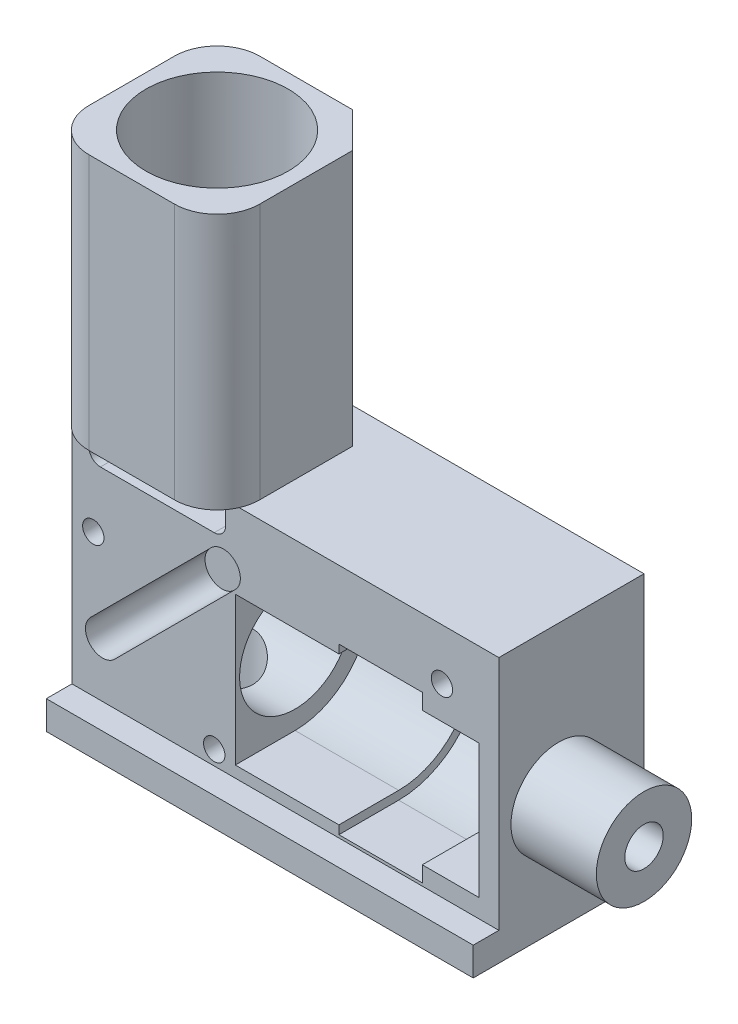
SolidWorks part; units mm, degrees
ref_plane "Front Plane" through (0, 0, 0) normal (0, 0, 1) x (1, 0, 0)
ref_plane "Top Plane" through (0, 0, 0) normal (0, 1, 0) x (1, 0, 0)
ref_plane "Right Plane" through (0, 0, 0) normal (1, 0, 0) x (0, 0, -1)
sketch "Sketch1" plane through (0, 0, 0) normal (0, 1, 0) x (1, 0, 0)
  line L1 (7.5, 3) -> (-7.5, 3)
  line L2 (7.5, 3) -> (7.5, -3)
  line L3 (7.5, -3) -> (-7.5, -3)
  line L4 (-7.5, 3) -> (-7.5, -3)
  line L5 (7.5, 3) -> (-7.5, -3) construction
  line L6 (7.5, -3) -> (-7.5, 3) construction
  point P0 (0, 0)
  dimension "D1" = 6
  dimension "D2" = 15
extrude "Main Body Ext" add sketch "Sketch1" along normal blind 9.3
sketch "Sketch8" plane through (0, 9.3, 0) normal (0, 1, 0) x (1, 0, 0)
  line L0 (-2.75, 3) -> (-1.5, 1.75)
  line L1 (-2.75, 3) -> (-7.5, 3)
  line L2 (-1.5, 1.75) -> (-1.5, -3)
  line L3 (-1.5, -3) -> (-7.5, -3)
  line L4 (-7.5, 3) -> (-7.5, -3)
  line L5 (-2.125, 2.375) -> (-7.5, -3) construction
  line L6 (-1.5, -3) -> (-7.5, 3) construction
  line L7 (-7.5, 3) -> (-7.5, -3) construction
  line L8 (0, 0) -> (-4.5, 0) construction
  point P0 (-4.5, 0)
  dimension "D1" = 6
  dimension "D2" = 6
  dimension "D3" = 1.25
  dimension "D4" = 3
extrude "Emission Path Ext" add sketch "Sketch8" along normal blind 9
sketch "Sketch3" plane through (0, 0, 0) normal (0, -1, 0) x (1, 0, 0)
  line L0 (-7.5, -3) -> (-7.5, 3) construction
  line L1 (0, 0) -> (-4.5, 0) construction
  circle A0 centre (-4.5, 0) radius 1.25
  dimension "D1" = 3
  dimension "D2" = 2.5
extrude "Emission and Grin Cut" cut sketch "Sketch3" against normal through all
sketch "Sketch4" plane through (7.5, 0, 0) normal (1, 0, 0) x (0, 0, -1)
  line L1 (-3, 0) -> (3, 0) construction
  circle A0 centre (0, 4) radius 0.675
  dimension "D1" = 1.35
  dimension "D2" = 4
extrude "Fiber Ferrule Cut" cut sketch "Sketch4" against normal offset from surface (13 mm away) 2 up to face at (-7.5, 9.15, 0)
sketch "Sketch41" plane through (7.5, 0, 0) normal (1, 0, 0) x (0, 0, -1)
  circle A0 centre (0, 4) radius 1.675
  circle A1 centre (0, 4) radius 0.675 construction
  circle A2 centre (0, 4) radius 0.675
  dimension "D1" = 1
extrude "Fiber Ferrule Port Ext" add sketch "Sketch41" along normal blind 3
sketch "Sketch5" plane through (0, 0, 3) normal (0, 0, 1) x (1, 0, 0)
  line L0 (-7.5, 0) -> (7.5, 0) construction
  line L1 (7.5, 9.3) -> (-7.5, 9.3)
  line L2 (7.5, 9.3) -> (7.5, 1)
  line L3 (7.5, 1) -> (-7.5, 1)
  line L4 (-7.5, 9.3) -> (-7.5, 1)
  line L5 (7.5, 9.3) -> (-7.5, 1) construction
  line L6 (7.5, 1) -> (-7.5, 9.3) construction
  line L7 (-1.5, 9.3) -> (7.5, 9.3) construction
  line L9 (7.5, 9.3) -> (7.5, 0) construction
  line L10 (-7.5, 18.3) -> (-7.5, 0) construction
  point P0 (0, 5.15)
  dimension "D1" = 1
extrude "FilterSet Cut1" cut sketch "Sketch5" against normal blind 0.9
sketch "Sketch6" plane through (0, 0, 2.1) normal (0, 0, 1) x (1, 0, 0)
  line L0 (3.4, 7.5) -> (3.4, 1.5)
  line L1 (3.4, 1.5) -> (-0.9, 1.5)
  line L3 (-7.5, 1) -> (7.5, 1) construction
  line L4 (-7.5, 9.3) -> (-7.5, 1) construction
  line L5 (-6.9, 8.9) -> (-6.9, 8.5)
  line L7 (-1.5, 9.3) -> (-7.5, 9.3) construction
  line L8 (-2.1, 8.9) -> (-2.1, 8.5)
  line L9 (-6, 2.5) -> (-6, 1) construction
  line L10 (-2.5, 9.3) -> (-6.5, 9.3)
  line L11 (-4.5, 4) -> (-4.5, 1) construction
  line L12 (-4.5, 4) -> (0.4851, 4) construction
  line L13 (-2.5, 8.1) -> (-6.5, 8.1)
  line L14 (-0.9, 1.5) -> (-0.9, 7.5)
  line L15 (-2.5, 9.3) -> (-6.5, 8.1) construction
  line L16 (-2.5, 8.1) -> (-6.5, 9.3) construction
  line L18 (-2.6059, 7.5912) -> (-6.8485, 3.3485)
  line L20 (-1.7574, 6.7426) -> (-6, 2.5)
  line L21 (-2.6059, 7.5912) -> (-6, 2.5) construction
  line L22 (-6.8485, 3.3485) -> (-1.7574, 6.7426) construction
  line L24 (-0.9, 7.5) -> (3.4, 7.5)
  line L33 (-2.5, 9.3) -> (1.102, 9.3) construction
  line L35 (1.102, 8.1) -> (-2.5, 8.1) construction
  line L36 (-6.5, 8.1) -> (-4.098, 8.1) construction
  line L38 (-4.098, 9.3) -> (-6.5, 9.3) construction
  arc A0 (-2.5, 9.3) -> (-2.1, 8.9) centre (-2.5, 8.9) cw
  arc A2 (-6.5, 9.3) -> (-6.9, 8.9) centre (-6.5, 8.9) ccw
  arc A3 (-2.6059, 7.5912) -> (-1.7574, 6.7426) centre (-2.1816, 7.1669) cw
  arc A5 (-6.8485, 3.3485) -> (-6, 2.5) centre (-6.4243, 2.9243) ccw
  arc A7 (-6.5, 8.1) -> (-6.9, 8.5) centre (-6.5, 8.5) cw
  arc A8 (-2.5, 8.1) -> (-2.1, 8.5) centre (-2.5, 8.5) ccw
  point P5 (-4.5, 8.7)
  point P10 (-4.3029, 5.0456)
  point P24 (-0.6861, 4)
  point P48 (-0.9, 4.5)
  line M12 (-1.5, 9.3) -> (-7.5, 9.3)
  dimension "D10" = 1.5
  dimension "D5" = 6.6
  dimension "D8" = 0.5
  dimension "D11" = 0.4
  dimension "D12" = 0.4
  dimension "D2" = 45
  dimension "D3" = 6
  dimension "D4" = 1.2
  dimension "D6" = 3
  dimension "D7" = 4
  dimension "D9" = 3
  dimension "D13" = 1.2
  dimension "D14" = 3
  dimension "D15" = 6
  dimension "D17" = 4.3
extrude "FilterSet Cut2" cut sketch "Sketch6" against normal offset from surface (4.2 mm away) 0.9 contours L18 A5 L20 A3 | L13 A8 L8 A0 A2 L5 A7 M12 up to face at (-0.0625, 9.95, -3)
sketch "Sketch39" plane through (0, 0, 0) normal (0, 0, 1) x (1, 0, 0)
  line L0 (-4.5, 4) -> (0.4851, 4) construction
  line L1 (-4.5, 4) -> (-0.9, 4) construction
  line L2 (0.6, 6.6) -> (1.88, 6.6)
  line L3 (1.88, 6.6) -> (1.88, 6.9)
  line L5 (3.4, 7.5) -> (3.4, 1.5) construction
  line L6 (3.4, 6.9) -> (4.81, 6.9)
  line L8 (4.81, 4) -> (3.4, 4)
  line L10 (3.4, 6.9) -> (1.88, 6.9)
  line L12 (3.4, 4) -> (-0.4058, 4)
  line L16 (-0.9, 6.6) -> (-1.76, 6.6)
  line L17 (-1.76, 6.6) -> (-1.76, 4)
  line L18 (-1.76, 4) -> (-0.9, 4)
  line L19 (-0.9, 6.6) -> (0.6, 6.6)
  line L22 (-0.5058, 4) -> (0.4851, 4) construction
  line L23 (-0.9, 4) -> (-0.4058, 4)
  line L24 (4.81, 4) -> (6.967, 4) construction
  line L26 (4.81, 4) -> (4.81, 6.9) construction
  line L27 (4.81, 4) -> (6.81, 4)
  line L30 (6.81, 4) -> (6.81, 6.35)
  line L31 (6.81, 6.35) -> (4.81, 6.35)
  line L32 (4.81, 6.35) -> (4.81, 6.9)
  dimension "D1" = 2.93
  dimension "D3" = 2.6
  dimension "D4" = 6.57
  dimension "D5" = 0.55
  dimension "D6" = 2
  dimension "D7" = 2.74
  dimension "D8" = 2.9
revolve "Excitation Lens Cut" cut sketch "Sketch39" angle 360 about L8
sketch "Sketch10" plane through (0, 18.3, 0) normal (0, 1, 0) x (1, 0, 0)
  line L0 (-4.5, 0) -> (-4.5, -3) construction
  line L1 (-7.5, -3) -> (-1.5, -3) construction
  line L3 (-4.5, 0) -> (-7.5, 0) construction
  line L4 (-7.5, 3) -> (-7.5, -3) construction
  circle A0 centre (-4.5, 0) radius 2.5
  dimension "D1" = 5
extrude "Emission Lens Cut" cut sketch "Sketch10" against normal offset from surface (8.5 mm away) 0.5 up to face at (-4.125, 9.3, 1.3313)
sketch "Sketch40" plane through (-1.76, 0, 0) normal (1, 0, 0) x (0, 0, -1)
  circle A0 centre (0, 4) radius 1.95
  dimension "D1" = 3.9
extrude "Excitation Pathway Cut" cut sketch "Sketch40" against normal up to surface (0.79 mm away)
sketch "Sketch44" plane through (0, 0, 0) normal (0, 0, 1) x (1, 0, 0)
  line L1 (3.4, 1.1) -> (1.88, 1.1)
  line L2 (4.81, 1.1) -> (3.4, 1.1)
  line L3 (4.81, 1.65) -> (4.81, 1.1)
  line L4 (6.81, 1.65) -> (4.81, 1.65)
  line L5 (-0.9, 1.4) -> (-1.76, 1.4)
  line L6 (0.6, 1.4) -> (-0.9, 1.4)
  line L7 (0.6, 1.4) -> (1.88, 1.4)
  line L8 (1.88, 1.4) -> (1.88, 1.1)
  line L14 (0.6, 6.6) -> (-0.9, 6.6)
  line L15 (-0.9, 6.6) -> (-1.76, 6.6)
  line L16 (-1.76, 6.6) -> (-1.76, 4)
  line L17 (-1.76, 4) -> (-0.9, 4)
  line L18 (-0.9, 4) -> (-0.4058, 4)
  line L19 (-0.4058, 4) -> (3.4, 4)
  line L20 (3.4, 4) -> (4.81, 4)
  line L21 (4.81, 4) -> (6.81, 4)
  line L22 (6.81, 4) -> (6.81, 6.35)
  line L23 (6.81, 6.35) -> (4.81, 6.35)
  line L24 (4.81, 6.35) -> (4.81, 6.9)
  line L25 (4.81, 6.9) -> (3.4, 6.9)
  line L26 (3.4, 6.9) -> (1.88, 6.9)
  line L27 (1.88, 6.9) -> (1.88, 6.6)
  line L28 (0.6, 6.6) -> (-0.9, 6.6)
  line L29 (-0.9, 6.6) -> (-1.76, 6.6)
  line L30 (-1.76, 6.6) -> (-1.76, 1.4)
  line L31 (-1.76, 4) -> (-0.9, 4) construction
  line L32 (-0.9, 4) -> (-0.4058, 4) construction
  line L33 (-0.4058, 4) -> (3.4, 4) construction
  line L34 (3.4, 4) -> (4.81, 4) construction
  line L35 (4.81, 4) -> (6.81, 4) construction
  line L36 (6.81, 1.65) -> (6.81, 6.35)
  line L37 (6.81, 6.35) -> (4.81, 6.35)
  line L38 (4.81, 6.35) -> (4.81, 6.9)
  line L39 (4.81, 6.9) -> (3.4, 6.9)
  line L40 (3.4, 6.9) -> (1.88, 6.9)
  line L50 (1.88, 6.9) -> (1.88, 6.6)
  line L51 (1.88, 6.6) -> (0.6, 6.6)
  line L52 (1.88, 6.6) -> (0.6, 6.6)
  dimension "D1" = 0
extrude "Excitation Pathway Cut 2" cut sketch "Sketch44" along normal up to surface (2.1 mm away) up to face at (3.0717, 4, 2.1)
sketch "Sketch15" plane through (0, 0, 0) normal (0, -1, 0) x (1, 0, 0)
  line L0 (-6.25, 1.875) -> (-6.25, -1.875) construction
  line L2 (-1.5, 0) -> (-4.5, 0) construction
  line L3 (-4.5, 0) -> (-6.25, 0) construction
  circle A0 centre (-6.25, -1.875) radius 0.795
  circle A1 centre (-6.25, 1.875) radius 0.795
  circle A2 centre (-1.5, 0) radius 0.795
  dimension "D4" = 1.59
  dimension "D1" = 3.75
  dimension "D2" = 3
  dimension "D3" = 1.75
extrude "Magnets Cut" cut sketch "Sketch15" against normal blind 0.9
sketch "Sketch18" plane through (0, 0, 2.1) normal (0, 0, 1) x (1, 0, 0)
  line L0 (-7.5, 9.3) -> (-7.5, 1) construction
  line L1 (7.5, 1) -> (7.5, 9.3) construction
  line L2 (7.5, 9.3) -> (-1.5, 9.3) construction
  line L3 (-7.5, 0) -> (7.5, 0) construction
  line L7 (-7.5, 1) -> (7.5, 1) construction
  line L9 (-7.5, 1) -> (-7.5, 0) construction
  circle A0 centre (-6.75, 6) radius 0.375
  circle A1 centre (5.5, 7.5) radius 0.375
  circle A2 centre (-2.5, 1.51) radius 0.375
  dimension "D1" = 0.75
  dimension "D2" = 0.75
  dimension "D3" = 1.8
  dimension "D4" = 2
  dimension "D5" = 5
  dimension "D6" = 1.51
  dimension "D7" = 5
extrude "Screw Holes Cut" cut sketch "Sketch18" against normal blind 3 and the other way through all
fillet "External Fillet 1" radius 1.5 2 edges at (-7.5, 9.15, -3)
sketch "Sketch14" plane through (0, 0, 0) normal (0, -1, 0) x (1, 0, 0)
  line L1 (7.5, -3) -> (-6, -3) construction
  line L2 (1.5, -2.0099) -> (0.8399, -3)
  line L3 (7.5, -3) -> (-6, -3) construction
  line L4 (0.8399, -3) -> (1.5, -3)
  line L5 (1.5, -3) -> (-7.5, 3) construction
  line L6 (-7.5, -1.5) -> (-7.5, 3) construction
  line L7 (-7.5, 3) -> (7.5, 3) construction
  line L8 (3.5, -2.0099) -> (4.4901, -3)
  line L9 (1.5, -2.0099) -> (3.5, -2.0099)
  line L11 (1.5, -3) -> (3.3387, -3)
  line M3 (-6, -3) -> (7.5, -3)
  dimension "D1" = 9
  dimension "D2" = 1.19
  dimension "D3" = 45
  dimension "D4" = 2
sketch "Sketch28" plane through (0, 8.1, 0) normal (0, 1, 0) x (1, 0, 0)
  circle A0 centre (-4.5, 0) radius 1.5
  dimension "D1" = 3
extrude "Emission Pathway Cut" cut sketch "Sketch28" against normal blind 4 and the other way through all
extrude "Small Baseplate Cut" [suppressed] cut sketch "Sketch14" against normal blind 1.5 contours L5 L2 M3 | L5 L8 L9 L2 M3
sketch "Sketch36" plane through (0, 18.3, 0) normal (0, 1, 0) x (1, 0, 0)
  line L0 (-7.5, -1.5) -> (-7.5, -3)
  line L1 (-7.5, 1.5) -> (-7.5, -3) construction
  line L2 (-7.5, -3) -> (-6, -3)
  line L3 (-7.5, -3) -> (-3, -3) construction
  line L4 (-9.9, 0) -> (9.9, 0) construction
  arc A0 (-7.5, -1.5) -> (-6, -3) centre (-6, -1.5) ccw
  dimension "D1" = 1.5
  dimension "D2" = 1.5
  dimension "D3" = 3
extrude "Cut-Extrude16" cut sketch "Sketch36" against normal up to surface (9 mm away) up to face at (-4.4051, 9.3, 1.3006)
sketch "Sketch37" plane through (0, 9.8, 0) normal (0, 1, 0) x (1, 0, 0)
  circle A0 centre (-4.5, 0) radius 2
  circle A1 centre (-4.5, 0) radius 1.5 construction
  dimension "D1" = 4
extrude "Cut-Extrude17" cut sketch "Sketch37" against normal up to next
ref_plane "Plane1" through (5.81, 0, 0) normal (-1, 0, 0) x (0, 0, 1)
sketch "Sketch43" plane through (5.81, 0, 0) normal (-1, 0, 0) x (0, 0, 1)
  line L0 (-3, 0) -> (-3, 18.3) construction
  line L1 (-3, 2.75) -> (-3, 5.25)
  line L3 (-3, 5.25) -> (-3, 5.8028)
  line L4 (-3, 2.75) -> (-3, 2.1972)
  line L5 (-3, 5.8028) -> (-3, 10.1818) construction
  line L6 (-2.75, 1.8349) -> (-2.75, 6.1651) construction
  line L7 (2.1, 9.3) -> (-3, 9.3) construction
  line L8 (2.1, 9.3) -> (-3, 9.3)
  arc A1 (-3, 5.8028) -> (-3, 2.1972) centre (0, 4) ccw
  arc A3 (-2.75, 6.1651) -> (-2.75, 1.8349) centre (0, 4) ccw construction
  arc A4 (-3, 5.25) -> (-3, 2.75) centre (0, 4) ccw construction
  point P13 (-3.5, 4)
  dimension "D1" = 3.4972
  dimension "D2" = 3.6056
  dimension "D3" = 0.5
extrude "Lens Wall Thickness Ext" add sketch "Sketch43" along normal blind 6 contours L1 L3 A1 L4
sketch "Sketch45" plane through (0, 0, 0) normal (0, -1, 0) x (1, 0, 0)
  line L0 (7.5, -3) -> (-7.5, 3) construction
  line L1 (7.5, -1.6639) -> (6.6093, -3)
  line L2 (7.5, 3) -> (7.5, -3) construction
  line L3 (7.5, -3) -> (-6, -3) construction
  dimension "D1" = 33.69
extrude "Baseplate Notch Cut" cut sketch "Sketch45" against normal blind 2 and the other way through all
